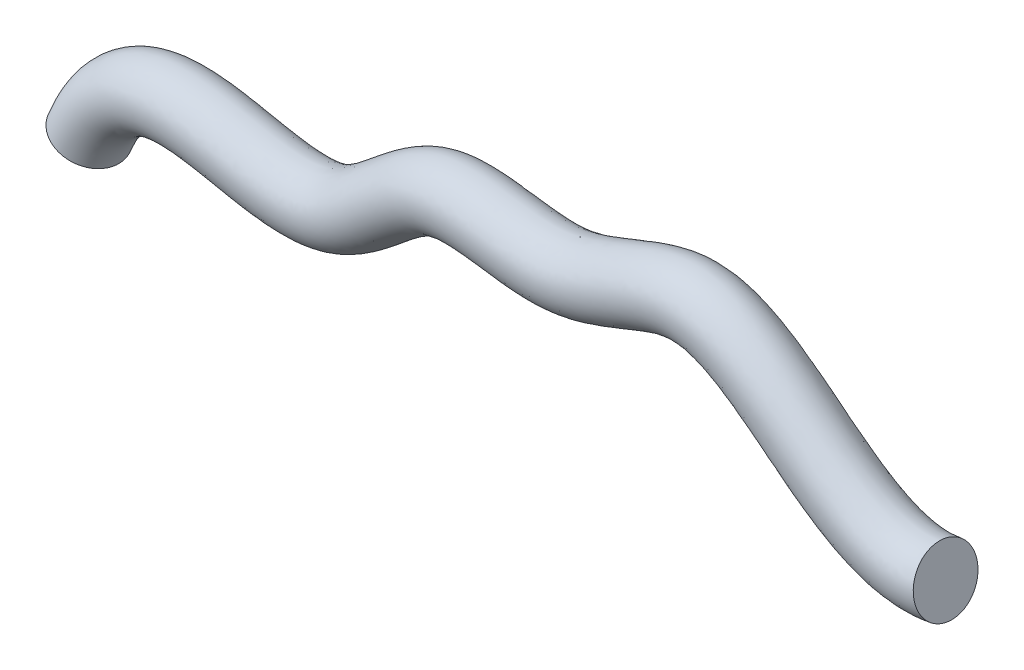
SolidWorks part; units mm, degrees
ref_plane "Front Plane" through (0, 0, 0) normal (0, 0, 1) x (1, 0, 0)
ref_plane "Top Plane" through (0, 0, 0) normal (0, 1, 0) x (1, 0, 0)
ref_plane "Right Plane" through (0, 0, 0) normal (1, 0, 0) x (0, 0, -1)
sketch "Sketch1" plane through (0, 0, 0) normal (0, 0, 1) x (1, 0, 0)
  spline S0 degree 3 poles (0, 0) (10.4277, 25.3707) (41.5055, -3.2313) (65.07, 29.0904) (90.6923, 17.8243) (123.3132, 41.8403) (142.9986, 4.0801) (161.4108, 7.638) knots 0 0 0 0 0.292067 0.417322 0.5572 0.698271 1 1 1 1
sweep "Sweep1" add path "Sketch1" circular profile diameter 12 parameters "D3"=12
